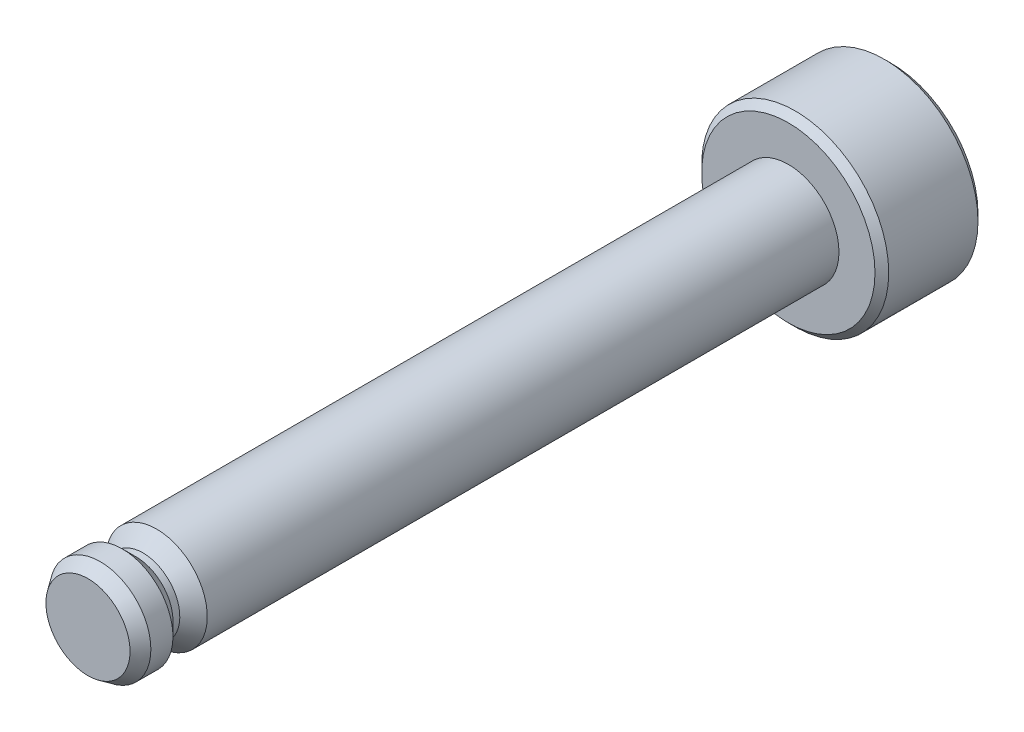
SolidWorks part; units mm, degrees
ref_plane "Front" through (0, 0, 0) normal (0, 0, 1) x (1, 0, 0)
ref_plane "Top" through (0, 0, 0) normal (0, 1, 0) x (1, 0, 0)
ref_plane "Right" through (0, 0, 0) normal (1, 0, 0) x (0, 0, -1)
sketch "Sketch2" plane through (0, 0, 0) normal (0, 0, 1) x (1, 0, 0)
  circle A0 centre (0, 0) radius 1.475
  dimension "D1" = 2.95
extrude "Shaft" add sketch "Sketch2" along normal blind 20.4
sketch "Sketch5" plane through (0, 0, 0) normal (0, 0, 1) x (1, 0, 0)
  circle A0 centre (0, 0) radius 2.725
  dimension "D1" = 5.45
extrude "Head" add sketch "Sketch5" against normal blind 3
chamfer "Chamfer1" distance 0.25 angle 55 1 edges at (1.475, 0, 20.4) first distance on face at (1.475, 0, 20.4)
chamfer "Deburs" distance 0.2 angle 45 2 edges at (2.725, 0, 0) (2.725, 0, -3)
sketch "Sketch6" plane through (0, 0, 0) normal (1, 0, 0) x (0, 0, -1)
  line L0 (0, 0) -> (-18.9, 0) construction
  line L1 (-18.9, 0) -> (-18.9, 1.075) construction
  line L2 (0, 1.475) -> (-20.043, 1.475) construction
  line L3 (-19.4, 1.475) -> (-18.4, 1.475)
  line L4 (-18.4, 1.475) -> (-18.8, 1.075)
  line L5 (-18.8, 1.075) -> (-19, 1.075)
  line L6 (-19, 1.075) -> (-19.4, 1.475)
  line L7 (-18.9, 1.075) -> (-18.9, 1.475) construction
  point P3 (0, 0)
  point P4 (0, 0)
  point P12 (0, 0)
  dimension "D1" = 18.9
  dimension "D2" = 0.4
  dimension "D3" = 1
revolve "e-Clip Notch Long" cut sketch "Sketch6" angle 360 about L0
equation "\"D1@Sketch2\"=\"Plastic Hardware OD@Box Assy.Assembly\""
equation "\"D1@Sketch5\"=\"Hardware Head Countersink Diameter@Box Assy.Assembly\"-.3mm"
equation "\"D1@Head\"=\"Countersink Depth@Box Assy.Assembly\""
equation "\"Length\"= 20mm"
equation "\"D1@Shaft\"=\"Length\"+.4mm"
equation "\"D1@Sketch6\"=\"Length\"-1.1mm"
